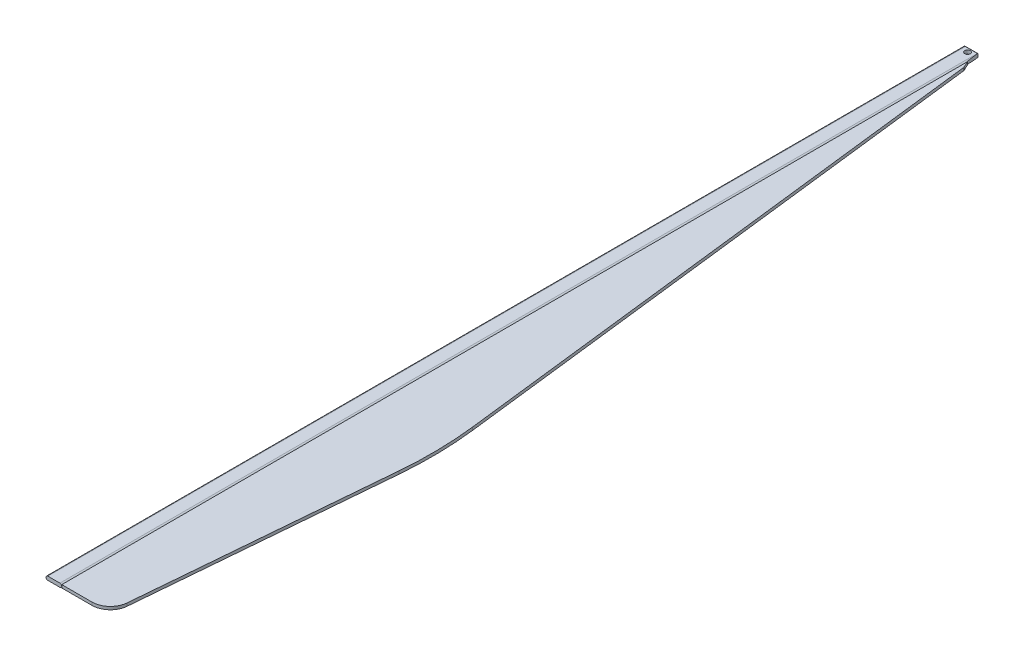
SolidWorks part; units mm, degrees
ref_plane "Front Plane" through (0, 0, 0) normal (0, 0, 1) x (1, 0, 0)
ref_plane "Top Plane" through (0, 0, 0) normal (0, 1, 0) x (1, 0, 0)
ref_plane "Right Plane" through (0, 0, 0) normal (1, 0, 0) x (0, 0, -1)
sketch "Sketch1" plane through (0, 0, 0) normal (0, 0, 1) x (1, 0, 0)
  line L0 (-165, 0) -> (165, 0) construction
  line L1 (-165, 50) -> (165, 50)
  line L2 (-165, -50) -> (165, -50)
  arc A0 (-165, 50) -> (-165, -50) centre (-165, 0) ccw
  arc A1 (165, -50) -> (165, 50) centre (165, 0) ccw
  point P3 (0, 0)
  point P8 (-215, 0)
  point P9 (215, 0)
  dimension "D2" = 100
  dimension "D1" = 430
sketch "Sketch2" plane through (0, 0, 0) normal (0, 1, 0) x (1, 0, 0)
  line L0 (0, 0) -> (0, -25000)
  dimension "D1" = 25000
sweep "Sweep1" add profiles "Sketch1" path "Sketch2"
sketch "Sketch3" plane through (0, 0, 0) normal (0, 1, 0) x (1, 0, 0)
  line L0 (215, -341.9041) -> (297.3375, -516.2353)
  line L1 (297.3375, -516.2353) -> (2091.4012, -15688.9813)
  line L2 (2123.5652, -17722.8698) -> (1535.1003, -24542.9822)
  line L3 (1036.9512, -25000) -> (215, -25000)
  line L5 (215, -341.9041) -> (215, -25000)
  line L9 (215, -25000) -> (215, 0) construction
  arc A0 (2091.4012, -15688.9813) -> (2123.5652, -17722.8698) centre (-7839.4169, -16863.2263) cw
  arc A1 (1535.1003, -24542.9822) -> (1036.9512, -25000) centre (1036.9512, -24500) cw
  point P3 (215, 0)
  point P8 (0, 0)
  point P9 (215, -116.0941)
  point P10 (215, -1435.5071)
  point P15 (215, -934.2475)
  point P16 (359.4506, -288.1471)
  point P17 (1803.6756, -17581.1221)
  point P18 (700.9331, -1846.5373)
  point P19 (215, -175.1061)
  point P22 (416.7924, -1915.176)
  point P23 (215, -1435.5071)
  point P24 (215, -1435.5071)
  point P25 (215, -322.0072)
  point P26 (240.9983, -656.7035)
  point P27 (265.267, -623.3906)
  point P28 (1039.8678, -24907.6321)
  point P29 (0, 0)
  point P30 (0, 0)
  point P31 (0, 0)
  point P32 (770.183, -25000)
  point P33 (919.9513, -25000)
  point P34 (1202.9438, -25000)
  point P35 (1101.4235, -25000)
  point P36 (1189.0664, -25000)
  point P37 (1036.9512, -25000)
  point P38 (297.3375, -516.2353)
  point P39 (215, -341.9041)
  dimension "D1" = 10000
  dimension "D2" = 500
sketch "Sketch4" plane through (0, 50, 0) normal (0, 1, 0) x (1, 0, 0)
  line L0 (0, 0) -> (0, -120) construction
  line L1 (165, 0) -> (-165, 0) construction
  circle A0 centre (0, -120) radius 75
  dimension "D1" = 150
  dimension "D2" = 120
extrude "Cut-Extrude1" cut sketch "Sketch4" against normal through all
fillet "Fillet1" radius 20 4 edges at (0, 50, 0) (215, 0, 0) (0, -50, 0) (-215, 0, 0)
extrude "Boss-Extrude1" add sketch "Sketch3" along normal blind 40 and the other way blind 40 separate body
sketch "Sketch6" plane through (0, 50, 0) normal (0, 1, 0) x (1, 0, 0)
  line L1 (-165, 0) -> (165, 0) construction
  line L2 (215, -341.9041) -> (215, -25000) construction
  line L3 (215, -340.9369) -> (215, 0)
  line L4 (215, 0) -> (165, 0)
  line L5 (215, -340.9369) -> (202.4539, -340.9369)
  line L6 (195, 0) -> (165, 0) construction
  line L7 (202.4539, -340.9369) -> (165, 0)
extrude "Cut-Extrude3" cut sketch "Sketch6" against normal through all
